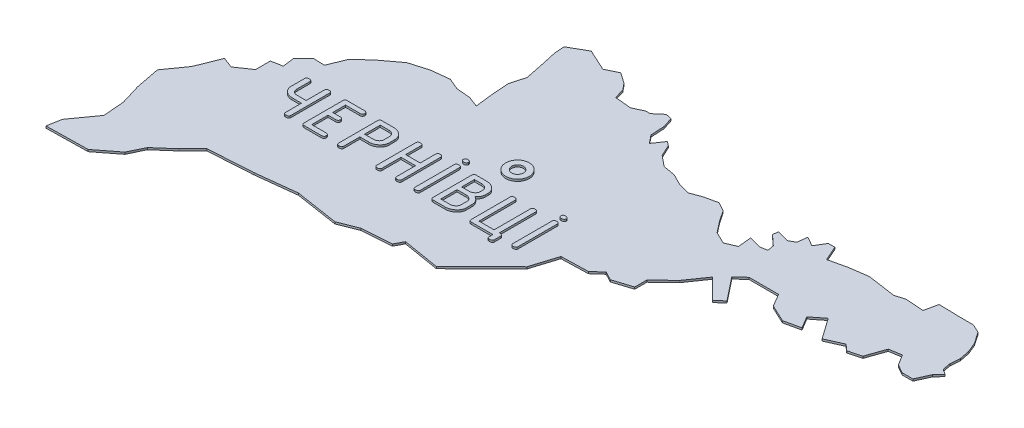
SolidWorks part; units mm, degrees
ref_plane "Спереди" through (0, 0, 0) normal (0, 0, 1) x (1, 0, 0)
ref_plane "Сверху" through (0, 0, 0) normal (0, 1, 0) x (1, 0, 0)
ref_plane "Справа" through (0, 0, 0) normal (1, 0, 0) x (0, 0, -1)
sketch "Эскиз1" plane through (0, 0, 0) normal (0, 1, 0) x (1, 0, 0)
  line B0 (-5205.415, 3609.1673) -> (-5161.2724, 3670.7877)
  line B1 (-5161.2724, 3670.7877) -> (-5165.8164, 3725.3443)
  line B2 (-5165.8164, 3725.3443) -> (-5181.3993, 3776.5482)
  line B3 (-5181.3993, 3776.5482) -> (-5193.7234, 3839.5402)
  line B4 (-5193.7234, 3839.5402) -> (-5157.3862, 3890.7949)
  line B5 (-5157.3862, 3890.7949) -> (-5133.3578, 3950.5103)
  line B6 (-5133.3578, 3950.5103) -> (-5106.1188, 3940.1166)
  line B7 (-5106.1188, 3940.1166) -> (-5069.1288, 3965.4251)
  line B8 (-5069.1288, 3965.4251) -> (-5069.1288, 4003.0603)
  line B9 (-5069.1288, 4003.0603) -> (-5053.5586, 4006.3115)
  line B10 (-5053.5586, 4006.3115) -> (-5041.2193, 4008.2699)
  line B11 (-5041.2193, 4008.2699) -> (-5045.1055, 4038.7626)
  line B12 (-5045.1055, 4038.7626) -> (-5019.1467, 4064.0711)
  line B13 (-5019.1467, 4064.0711) -> (-4990.6022, 4062.7757)
  line B14 (-4990.6022, 4062.7757) -> (-4973.0711, 4106.8879)
  line B15 (-4973.0711, 4106.8879) -> (-4937.3866, 4139.311)
  line B16 (-4937.3866, 4139.311) -> (-4891.3237, 4173.7178)
  line B17 (-4891.3237, 4173.7178) -> (-4845.238, 4187.3627)
  line B18 (-4845.238, 4187.3627) -> (-4799.17, 4192.5469)
  line B19 (-4799.17, 4192.5469) -> (-4769.9651, 4180.2228)
  line B20 (-4769.9651, 4180.2228) -> (-4734.2781, 4176.997)
  line B21 (-4734.2781, 4176.997) -> (-4707.0188, 4166.6033)
  line B22 (-4707.0188, 4166.6033) -> (-4712.2105, 4211.3784)
  line B23 (-4712.2105, 4211.3784) -> (-4715.4592, 4257.4464)
  line B24 (-4715.4592, 4257.4464) -> (-4705.063, 4294.4186)
  line B25 (-4705.063, 4294.4186) -> (-4714.1587, 4339.1938)
  line B26 (-4714.1587, 4339.1938) -> (-4723.8818, 4383.3313)
  line B27 (-4723.8818, 4383.3313) -> (-4725.8453, 4409.3028)
  line B28 (-4725.8453, 4409.3028) -> (-4681.7153, 4434.6114)
  line B29 (-4681.7153, 4434.6114) -> (-4626.5617, 4409.3028)
  line B30 (-4626.5617, 4409.3028) -> (-4596.0411, 4424.2177)
  line B31 (-4596.0411, 4424.2177) -> (-4568.7844, 4405.4141)
  line B32 (-4568.7844, 4405.4141) -> (-4555.1446, 4388.5409)
  line B33 (-4555.1446, 4388.5409) -> (-4548.0122, 4363.2069)
  line B34 (-4548.0122, 4363.2069) -> (-4505.8432, 4359.3182)
  line B35 (-4505.8432, 4359.3182) -> (-4479.8844, 4371.6677)
  line B36 (-4479.8844, 4371.6677) -> (-4468.2156, 4371.6677)
  line B37 (-4468.2156, 4371.6677) -> (-4446.1532, 4390.4713)
  line B38 (-4446.1532, 4390.4713) -> (-4430.5677, 4387.2455)
  line B39 (-4430.5677, 4387.2455) -> (-4422.1451, 4361.2765)
  line B40 (-4422.1451, 4361.2765) -> (-4420.1969, 4325.5743)
  line B41 (-4420.1969, 4325.5743) -> (-4403.3237, 4304.8123)
  line B42 (-4403.3237, 4304.8123) -> (-4384.5074, 4332.0792)
  line B43 (-4384.5074, 4332.0792) -> (-4374.1061, 4323.6413)
  line B44 (-4374.1061, 4323.6413) -> (-4360.5044, 4294.4186)
  line B45 (-4360.5044, 4294.4186) -> (-4333.2375, 4272.3638)
  line B46 (-4333.2375, 4272.3638) -> (-4302.7194, 4267.1797)
  line B47 (-4302.7194, 4267.1797) -> (-4275.4779, 4253.5348)
  line B48 (-4275.4779, 4253.5348) -> (-4244.3248, 4245.0969)
  line B49 (-4244.3248, 4245.0969) -> (-4215.765, 4255.516)
  line B50 (-4215.765, 4255.516) -> (-4183.314, 4262.6305)
  line B51 (-4183.314, 4262.6305) -> (-4160.6216, 4250.3065)
  line B52 (-4160.6216, 4250.3065) -> (-4142.453, 4223.0396)
  line B53 (-4142.453, 4223.0396) -> (-4119.7352, 4193.8702)
  line B54 (-4119.7352, 4193.8702) -> (-4089.2425, 4178.9274)
  line B55 (-4089.2425, 4178.9274) -> (-4061.9782, 4190.6165)
  line B56 (-4061.9782, 4190.6165) -> (-4065.2294, 4224.9979)
  line B57 (-4065.2294, 4224.9979) -> (-4034.7367, 4216.56)
  line B58 (-4034.7367, 4216.56) -> (-4015.8822, 4219.8138)
  line B59 (-4015.8822, 4219.8138) -> (-4019.136, 4236.687)
  line B60 (-4019.136, 4236.687) -> (-4045.1049, 4260.6747)
  line B61 (-4045.1049, 4260.6747) -> (-4043.1491, 4274.3196)
  line B62 (-4043.1491, 4274.3196) -> (-4012.6564, 4265.8843)
  line B63 (-4012.6564, 4265.8843) -> (-3997.0786, 4274.3196)
  line B64 (-3997.0786, 4274.3196) -> (-3993.8249, 4299.6282)
  line B65 (-3993.8249, 4299.6282) -> (-3969.8117, 4286.0087)
  line B66 (-3969.8117, 4286.0087) -> (-3954.2364, 4311.9777)
  line B67 (-3954.2364, 4311.9777) -> (-3937.3886, 4311.9777)
  line B68 (-3937.3886, 4311.9777) -> (-3920.49, 4274.3196)
  line B69 (-3920.49, 4274.3196) -> (-3874.4449, 4284.7133)
  line B70 (-3874.4449, 4284.7133) -> (-3828.3515, 4291.1674)
  line B71 (-3828.3515, 4291.1674) -> (-3792.0143, 4286.0087)
  line B72 (-3792.0143, 4286.0087) -> (-3756.3374, 4280.7992)
  line B73 (-3756.3374, 4280.7992) -> (-3731.0263, 4287.9391)
  line B74 (-3731.0263, 4287.9391) -> (-3684.9583, 4284.7133)
  line B75 (-3684.9583, 4284.7133) -> (-3677.793, 4318.4572)
  line B76 (-3677.793, 4318.4572) -> (-3621.3542, 4317.1364)
  line B77 (-3621.3542, 4317.1364) -> (-3588.9057, 4317.1364)
  line B78 (-3588.9057, 4317.1364) -> (-3566.8229, 4306.7681)
  line B79 (-3566.8229, 4306.7681) -> (-3546.7239, 4277.548)
  line B80 (-3546.7239, 4277.548) -> (-3536.3302, 4252.2623)
  line B81 (-3536.3302, 4252.2623) -> (-3531.1715, 4226.2933)
  line B82 (-3531.1715, 4226.2933) -> (-3533.1019, 4200.9847)
  line B83 (-3533.1019, 4200.9847) -> (-3529.1903, 4180.2228)
  line B84 (-3529.1903, 4180.2228) -> (-3515.5683, 4171.7874)
  line B85 (-3515.5683, 4171.7874) -> (-3531.1715, 4154.9142)
  line B86 (-3531.1715, 4154.9142) -> (-3546.7239, 4120.5074)
  line B87 (-3546.7239, 4120.5074) -> (-3573.9629, 4120.5074)
  line B88 (-3573.9629, 4120.5074) -> (-3596.0202, 4132.8315)
  line B89 (-3596.0202, 4132.8315) -> (-3612.9189, 4160.0984)
  line B90 (-3612.9189, 4160.0984) -> (-3644.0466, 4154.9142)
  line B91 (-3644.0466, 4154.9142) -> (-3660.9198, 4106.8879)
  line B92 (-3660.9198, 4106.8879) -> (-3693.3683, 4098.4526)
  line B93 (-3693.3683, 4098.4526) -> (-3708.9715, 4112.0974)
  line B94 (-3708.9715, 4112.0974) -> (-3751.1279, 4093.2938)
  line B95 (-3751.1279, 4093.2938) -> (-3788.7859, 4146.4789)
  line B96 (-3788.7859, 4146.4789) -> (-3819.2786, 4122.4657)
  line B97 (-3819.2786, 4122.4657) -> (-3801.0846, 4091.9476)
  line B98 (-3801.0846, 4091.9476) -> (-3841.971, 4082.8747)
  line B99 (-3841.971, 4082.8747) -> (-3886.1086, 4103.6342)
  line B100 (-3886.1086, 4103.6342) -> (-3904.9401, 4136.0852)
  line B101 (-3904.9401, 4136.0852) -> (-3980.2054, 4136.0852)
  line B102 (-3980.2054, 4136.0852) -> (-4003.5582, 4115.3232)
  line B103 (-4003.5582, 4115.3232) -> (-3956.1922, 4055.6078)
  line B104 (-3956.1922, 4055.6078) -> (-3976.3167, 4038.7626)
  line B105 (-3976.3167, 4038.7626) -> (-4027.5713, 4090.0147)
  line B106 (-4027.5713, 4090.0147) -> (-4061.9782, 4040.693)
  line B107 (-4061.9782, 4040.693) -> (-4104.7949, 3999.8066)
  line B108 (-4104.7949, 3999.8066) -> (-4104.7949, 3968.6535)
  line B109 (-4104.7949, 3968.6535) -> (-4152.1609, 3953.7361)
  line B110 (-4152.1609, 3953.7361) -> (-4174.2436, 3965.4251)
  line B111 (-4174.2436, 3965.4251) -> (-4198.2568, 3944.0053)
  line B112 (-4198.2568, 3944.0053) -> (-4266.3821, 3942.0724)
  line B113 (-4266.3821, 3942.0724) -> (-4287.1415, 3875.8774)
  line B114 (-4287.1415, 3875.8774) -> (-4403.3237, 3760.9958)
  line B115 (-4403.3237, 3760.9958) -> (-4497.4154, 3776.5482)
  line B116 (-4497.4154, 3776.5482) -> (-4509.0918, 3754.5162)
  line B117 (-4509.0918, 3754.5162) -> (-4584.3571, 3749.3321)
  line B118 (-4584.3571, 3749.3321) -> (-4631.7433, 3730.5031)
  line B119 (-4631.7433, 3730.5031) -> (-4741.4129, 3747.3763)
  line B120 (-4741.4129, 3747.3763) -> (-4843.2923, 3735.7126)
  line B121 (-4843.2923, 3735.7126) -> (-4956.1877, 3728.5727)
  line B122 (-4956.1877, 3728.5727) -> (-4991.9026, 3692.8704)
  line B123 (-4991.9026, 3692.8704) -> (-5034.727, 3655.2099)
  line B124 (-5034.727, 3655.2099) -> (-5053.5586, 3616.3072)
  line B125 (-5053.5586, 3616.3072) -> (-5106.1188, 3575.4208)
  line B126 (-5106.1188, 3575.4208) -> (-5211.8819, 3573.4904)
  line B127 (-5211.8819, 3573.4904) -> (-5205.415, 3609.1673)
sketch_block_instance "Блок8-1"
sketch_block "Блок8"
extrude "Бобышка-Вытянуть1" add sketch "Эскиз1" along normal blind 5 contours B127 B126 B125 B124 B123 B122 B121 B120 B119 B118 B117 B116 B115 B114 B113 B112 B111 B110 B109 B108 B107 B106 B105 B104 B103 B102 B101 B100 B99 B98 B97 B96 B95 B94 B93 B92 B91 B90 B89 B88 B87 B86 B85 B84 B83 B82 B81 B80 B79 B78 B77 region at (-4503.2277, 0, -4036.1783)
sketch "Эскиз2" plane through (0, 0, 0) normal (0, 1, 0) x (1, 0, 0)
  line L0 (-4990.6641, 3898.6682) -> (-3956.0852, 3898.6682) construction
  circle A0 centre (-4508.7755, 4073.7293) radius 15
  circle A1 centre (-4508.7755, 4073.7293) radius 30
  text T0 "<b>ЧЕРНІВЦІ</b>" font "GOST Type AU" height 110
  dimension "D1" = 30
  dimension "D2" = 60
extrude "Бобышка-Вытянуть2" add sketch "Эскиз2" along normal blind 10
scale "Масштаб1" scale about centroid uniform scaling yes scale factor 0.05
